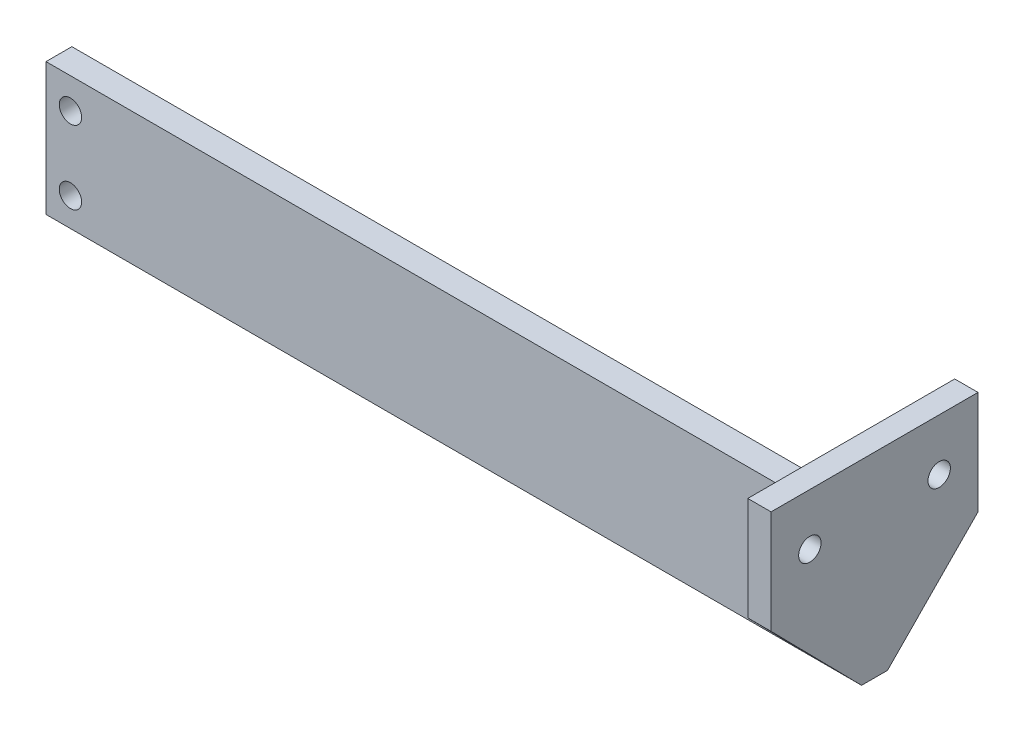
SolidWorks part; units mm, degrees
ref_plane "Front Plane" through (0, 0, 0) normal (0, 0, 1) x (1, 0, 0)
ref_plane "Top Plane" through (0, 0, 0) normal (0, 1, 0) x (1, 0, 0)
ref_plane "Right Plane" through (0, 0, 0) normal (1, 0, 0) x (0, 0, -1)
sketch "Sketch1" plane through (0, 0, 0) normal (0, 0, 1) x (1, 0, 0)
  line L1 (0, 0) -> (194.5, 0)
  line L2 (0, 0) -> (0, 32.5)
  line L3 (0, 32.5) -> (194.5, 32.5)
  line L4 (194.5, 0) -> (194.5, 32.5)
  dimension "D1" = 194.5
  dimension "D2" = 32.5
extrude "Boss-Extrude1" add sketch "Sketch1" along normal blind 6.35
sketch "Sketch2" plane through (0, 0, 6.35) normal (0, 0, 1) x (1, 0, 0)
  line L0 (0, 32.5) -> (0, 0) construction
  line L1 (0, 0) -> (194.5, 0) construction
  circle A0 centre (6, 25) radius 2.75
  circle A1 centre (6, 7) radius 2.75
  dimension "D1" = 5.5
  dimension "D2" = 6
  dimension "D3" = 18
  dimension "D4" = 25
extrude "Cut-Extrude1" cut sketch "Sketch2" against normal through all
sketch "Sketch3" plane through (194.5, 0, 0) normal (1, 0, 0) x (0, 0, -1)
  line L0 (-3.175, 32.5) -> (-3.175, 39.5009) construction
  line L1 (-28.575, 22.594) -> (22.225, 22.594)
  line L2 (-28.575, 22.594) -> (-28.575, 39.5009)
  line L3 (-28.575, 39.5009) -> (22.225, 39.5009)
  line L4 (22.225, 22.594) -> (22.225, 39.5009)
  line L5 (-6.35, 32.5) -> (0, 32.5) construction
  line L7 (-28.575, 22.594) -> (-6.35, 0)
  line L8 (-6.35, 0) -> (0, 0)
  line L9 (22.225, 22.594) -> (0, 0)
  line L11 (-28.575, 39.5009) -> (22.225, 39.5009)
  line L12 (-28.575, 39.5009) -> (-28.575, 47.994)
  line L13 (-28.575, 47.994) -> (22.225, 47.994)
  line L14 (22.225, 39.5009) -> (22.225, 47.994)
  point P9 (-3.175, 39.5009)
  line M4 (0, 0) -> (0, 32.5)
  line M5 (0, 32.5) -> (-6.35, 32.5)
  line M6 (-6.35, 32.5) -> (-6.35, 0)
  line M7 (-6.35, 0) -> (0, 0)
  dimension "D1" = 25.4
  dimension "D2" = 50.8
  dimension "D3" = 15.494
extrude "Boss-Extrude2" add sketch "Sketch3" along normal blind 5.715 contours L1 L4 L3 L2 M6 M5 M4 | L1 L7 M6 | L1 M6 M4 M5 | L1 M6 M7 M4 | L9 L1 M4 | L3 L14 L13 L12 | L0 L3 L2 L1 M5 M6 region at (194.5, 31.3241, 16.7532) region at (194.5, 31.3241, -10.4032) region at (194.5, 27.547, 3.175) region at (194.5, 43.7475, 3.175) region at (194.5, 11.297, 3.175) region at (194.5, 15.0627, -7.4083) region at (194.5, 15.0627, 13.7583)
sketch "Sketch4" plane through (200.215, 0, 0) normal (1, 0, 0) x (0, 0, -1)
  line L0 (-28.575, 22.594) -> (-28.575, 47.994) construction
  line L1 (-28.575, 47.994) -> (22.225, 47.994) construction
  circle A0 centre (-19.05, 35.294) radius 2.75
  circle A1 centre (12.7, 35.294) radius 2.75
  dimension "D1" = 5.5
  dimension "D2" = 31.75
  dimension "D3" = 9.525
  dimension "D4" = 12.7
extrude "Cut-Extrude2" cut sketch "Sketch4" against normal through all
